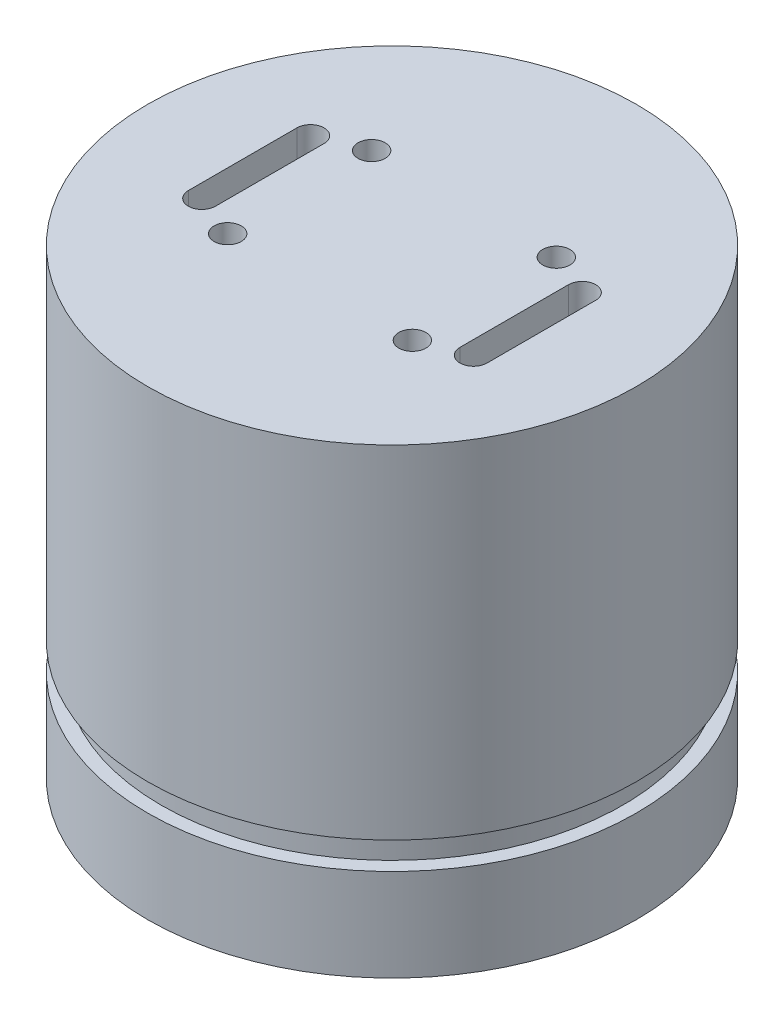
SolidWorks part; units mm, degrees
ref_plane "Front Plane" through (0, 0, 0) normal (0, 0, 1) x (1, 0, 0)
ref_plane "Top Plane" through (0, 0, 0) normal (0, 1, 0) x (1, 0, 0)
ref_plane "Right Plane" through (0, 0, 0) normal (1, 0, 0) x (0, 0, -1)
sketch "Sketch1" plane through (0, 0, 0) normal (0, 1, 0) x (1, 0, 0)
  circle A0 centre (0, 0) radius 90
  dimension "D1" = 180
extrude "Boss-Extrude1" add sketch "Sketch1" along normal blind 10
sketch "Sketch2" plane through (0, 10, 0) normal (0, 1, 0) x (1, 0, 0)
  line L1 (-34, 26.5) -> (34, 26.5) construction
  line L2 (-34, 26.5) -> (-34, -26.5) construction
  line L3 (-34, -26.5) -> (34, -26.5) construction
  line L4 (34, 26.5) -> (34, -26.5) construction
  line L5 (-34, 26.5) -> (34, -26.5) construction
  line L6 (-34, -26.5) -> (34, 26.5) construction
  circle A0 centre (-34, -26.5) radius 5
  circle A1 centre (34, -26.5) radius 5
  circle A2 centre (34, 26.5) radius 5
  circle A3 centre (-34, 26.5) radius 5
  point P0 (0, 0)
  dimension "D3" = 10
  dimension "D1" = 68
  dimension "D2" = 53
extrude "Cut-Extrude1" cut sketch "Sketch2" against normal through all
sketch "Sketch3" plane through (0, 0, 0) normal (0, -1, 0) x (1, 0, 0)
  circle A0 centre (0, 0) radius 90
  circle A1 centre (0, 0) radius 80
  circle A2 centre (0, 0) radius 90 construction
  circle A3 centre (0, 0) radius 90
  circle M7 centre (0, 0) radius 90
  dimension "D2" = 10
extrude "Boss-Extrude2" add sketch "Sketch3" along normal blind 150 contours A1 M7 region at (-87.4544, 0, 0)
sketch "Sketch4" plane through (0, 10, 0) normal (0, 1, 0) x (1, 0, 0)
  line L0 (50, 20) -> (50, -20) construction
  line L1 (55, 20) -> (55, -20)
  line L2 (45, 20) -> (45, -20)
  arc A0 (55, 20) -> (45, 20) centre (50, 20) ccw
  arc A1 (45, -20) -> (55, -20) centre (50, -20) ccw
  point P2 (50, 0)
  dimension "D2" = 5
  dimension "D1" = 50
  dimension "D3" = 20
extrude "Cut-Extrude2" cut sketch "Sketch4" against normal through all
mirror "Mirror1" about plane through (0, 0, 0) normal (1, 0, 0) of "Cut-Extrude2"
sketch "Sketch8" plane through (0, -150, 0) normal (0, -1, 0) x (1, 0, 0)
  circle A0 centre (0, 0) radius 90 construction
  circle A1 centre (0, 0) radius 90
extrude "Boss-Extrude4" add sketch "Sketch8" along normal blind 10
sketch "Sketch9" plane through (0, -160, 0) normal (0, -1, 0) x (1, 0, 0)
  line L0 (0, -99.0098) -> (0, 98.2841) construction
  line L1 (-111.9692, 0) -> (108.5479, 0) construction
  circle A0 centre (6.5, 15.5) radius 1.5
  circle A1 centre (37.5, 15.5) radius 1.5
  circle A2 centre (6.5, -15.5) radius 1.5
  circle A3 centre (37.5, -15.5) radius 1.5
  circle A4 centre (-6.5, -15.5) radius 1.5
  circle A5 centre (-37.5, -15.5) radius 1.5
  circle A6 centre (-37.5, 15.5) radius 1.5
  circle A7 centre (-6.5, 15.5) radius 1.5
  dimension "D1" = 3
  dimension "D4" = 5
  dimension "D2" = 31
  dimension "D3" = 31
extrude "Cut-Extrude3" cut sketch "Sketch9" against normal up to next
sketch "Sketch10" plane through (0, -160, 0) normal (0, -1, 0) x (1, 0, 0)
  circle A0 centre (0, 0) radius 85
  circle A1 centre (0, 0) radius 90
  circle A2 centre (0, 0) radius 90
  dimension "D2" = 5
  dimension "D1" = 0
extrude "Cut-Extrude4" cut sketch "Sketch10" against normal blind 10 from offset 34 offset against normal yes
sketch "Sketch11" plane through (0, 0, 0) normal (0, 0, 1) x (1, 0, 0)
  line L0 (-90, -160) -> (90, -160) construction
  line L1 (0, -160) -> (90, -160) construction
  line L2 (0, -160) -> (0, 0) construction
  circle A0 centre (85, -160) radius 2.5
  point P4 (0, -160)
  point P8 (90, -160)
  dimension "D3" = 5
  dimension "D1" = 5
  dimension "D2" = 90
revolve "Cut-Revolve1" cut sketch "Sketch11" angle 360 about L2
